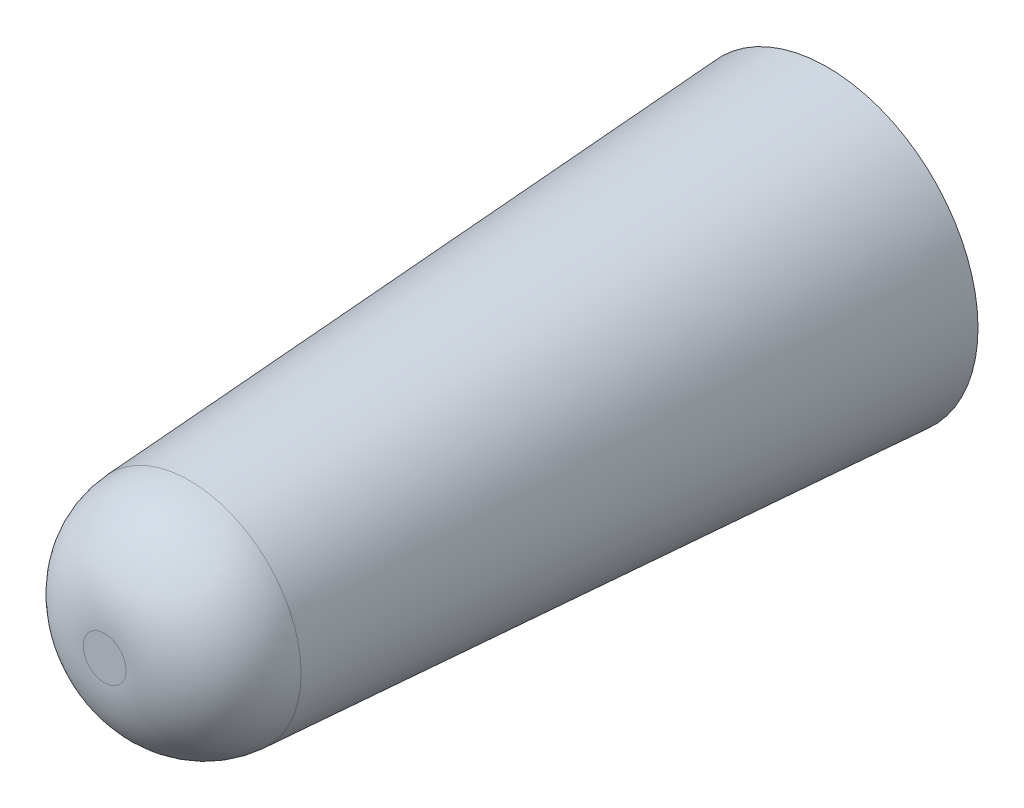
SolidWorks part; units mm, degrees
ref_plane "Front Plane" through (0, 0, 0) normal (0, 0, 1) x (1, 0, 0)
ref_plane "Top Plane" through (0, 0, 0) normal (0, 1, 0) x (1, 0, 0)
ref_plane "Right Plane" through (0, 0, 0) normal (1, 0, 0) x (0, 0, -1)
sketch "Sketch1" plane through (0, 0, 0) normal (0, 0, 1) x (1, 0, 0)
  circle A0 centre (-76.2, 0) radius 63.5
extrude "Boss-Extrude1" add sketch "Sketch1" along normal blind 304.8 draft 3.5
fillet "Fillet2" radius 38.1 1 edges at (-31.3424, 0, 304.8)
shell "Shell2" thickness 1.5875 removed face at (-12.7, 0, 0)
